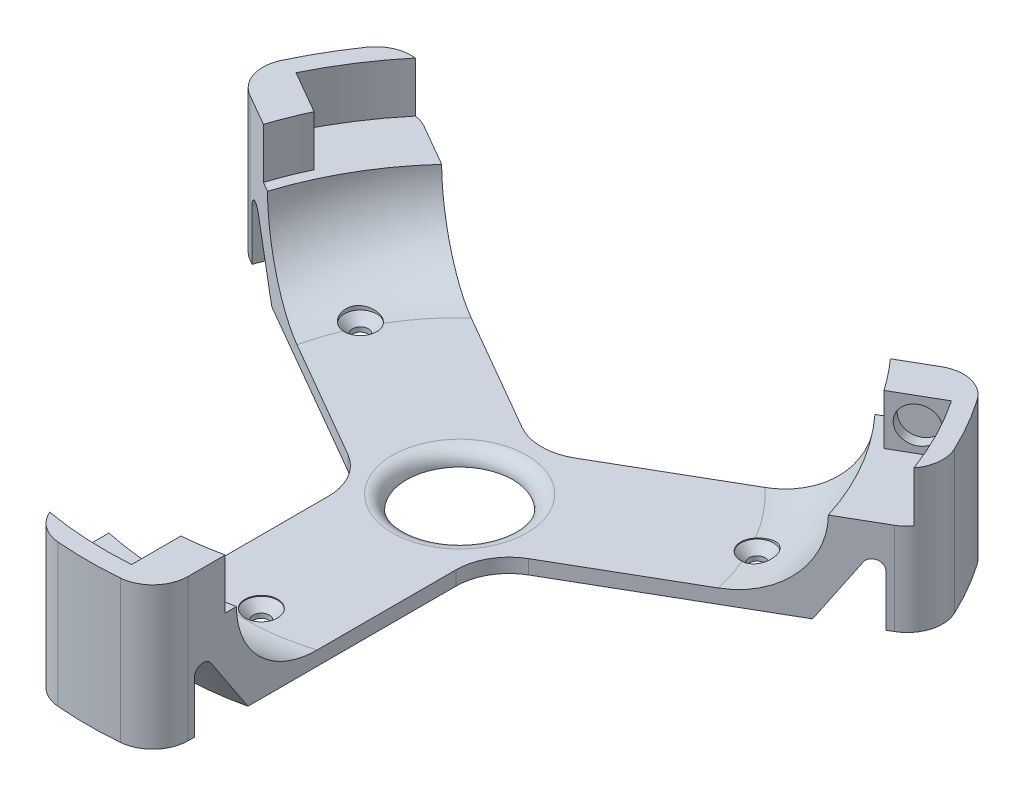
SolidWorks part; units mm, degrees
ref_plane "Front Plane" through (0, 0, 0) normal (0, 0, 1) x (1, 0, 0)
ref_plane "Top Plane" through (0, 0, 0) normal (0, 1, 0) x (1, 0, 0)
ref_plane "Right Plane" through (0, 0, 0) normal (1, 0, 0) x (0, 0, -1)
sketch "Sketch1" plane through (0, 0, 0) normal (0, 1, 0) x (1, 0, 0)
  line L0 (-56, 0) -> (-56, 28)
  line L1 (-28, 0) -> (-28, 28)
  line L3 (-28, 0) -> (-28, 28)
  line L4 (28, 0) -> (28, 28)
  line L5 (28, 0) -> (28, 28)
  line L7 (56, 0) -> (56, 28)
  line L8 (0, 0) -> (0, 28)
  line L9 (56, 0) -> (56, 28)
  line L10 (-56, 28) -> (-56, 56)
  line L11 (-56, 56) -> (-28, 56)
  line L12 (-28, 28) -> (-28, 56)
  line L13 (-28, 28) -> (-28, 56)
  line L15 (0, 56) -> (28, 56)
  line L16 (28, 28) -> (28, 56)
  line L17 (28, 28) -> (28, 56)
  line L18 (28, 56) -> (56, 56)
  line L19 (56, 28) -> (56, 56)
  line L20 (-28, 56) -> (0, 56)
  line L21 (56, 28) -> (56, 56)
  line L23 (0, 28) -> (0, 56)
  line L24 (-56, -28) -> (-56, 0)
  line L25 (-28, -28) -> (-28, 0)
  line L27 (-28, -28) -> (-28, 0)
  line L28 (28, -28) -> (28, 0)
  line L29 (28, -28) -> (28, 0)
  line L31 (56, -28) -> (56, 0)
  line L32 (0, -28) -> (0, 0)
  line L33 (56, -28) -> (56, 0)
  line L34 (-56, 0) -> (-56, 28)
  line L35 (-56, 28) -> (-28, 28)
  line L36 (-28, 0) -> (-28, 28)
  line L37 (-28, 0) -> (-28, 28)
  line L38 (0, 0) -> (0, 28)
  line L39 (0, 28) -> (28, 28)
  line L40 (28, 0) -> (28, 28)
  line L41 (28, 0) -> (28, 28)
  line L42 (28, 28) -> (56, 28)
  line L43 (56, 0) -> (56, 28)
  line L44 (-28, 28) -> (0, 28)
  line L45 (56, 0) -> (56, 28)
  line L46 (0, 0) -> (0, 28)
  line L47 (0, 0) -> (0, 28)
  line L48 (28, -56) -> (56, -56)
  line L49 (0, -56) -> (28, -56)
  line L51 (0, -28) -> (28, -28)
  line L52 (28, -56) -> (28, -28)
  line L53 (28, -56) -> (28, -28)
  line L54 (-28, -56) -> (0, -56)
  line L55 (56, -56) -> (56, -28)
  line L56 (-56, -56) -> (-28, -56)
  line L57 (56, -56) -> (56, -28)
  line L58 (-56, -56) -> (-56, -28)
  line L59 (-56, -28) -> (-28, -28)
  line L60 (28, -28) -> (56, -28)
  line L61 (0, -28) -> (28, -28)
  line L62 (0, -28) -> (0, 0)
  line L63 (0, 0) -> (28, 0)
  line L64 (28, -28) -> (28, 0)
  line L65 (28, -28) -> (28, 0)
  line L66 (28, 0) -> (56, 0)
  line L67 (56, -28) -> (56, 0)
  line L68 (-28, -56) -> (-28, -28)
  line L69 (56, -28) -> (56, 0)
  line L70 (-28, -56) -> (-28, -28)
  line L72 (84, 0) -> (84, 28)
  line L81 (0, -56) -> (0, -28)
  line L82 (-28, -28) -> (0, -28)
  line L83 (-56, -28) -> (-28, -28)
  line L84 (-56, -28) -> (-56, 0)
  line L85 (-56, 0) -> (-28, 0)
  line L86 (-28, -28) -> (-28, 0)
  line L87 (-28, -28) -> (-28, 0)
  line L88 (-28, 0) -> (0, 0)
  line L89 (0, -28) -> (0, 0)
  line L90 (0, -28) -> (0, 0)
  line L92 (0, -56) -> (0, -28)
  line L93 (0, -28) -> (0, 0)
  line L94 (0, 0) -> (0, 28)
  line L95 (0, 28) -> (0, 56)
  dimension "D3" = 3
  dimension "D4" = 2
  dimension "D5" = 3
  dimension "D6" = 2
sketch "Sketch2" plane through (0, 0, 0) normal (0, 1, 0) x (1, 0, 0)
  circle A0 centre (0, 0) radius 83
  circle A1 centre (0, 0) radius 105
  dimension "D1" = 166
  dimension "D2" = 22
extrude "Boss-Extrude1" add sketch "Sketch2" along normal blind 22
sketch "Sketch4" plane through (0, 0, 0) normal (0, 0, 1) x (1, 0, 0)
  line L2 (105, 22) -> (-105, 22) construction
  line L3 (-105, 0) -> (105, 0) construction
  line L4 (83, 22) -> (83, 0)
  line L5 (83, 0) -> (61, 0)
  ellipse E0 centre (61, 22) end of major axis (61, 44) minor radius 22 (61, 0) -> (83, 22) ccw
  dimension "D1" = 22
revolve "Revolve5" add sketch "Sketch4" angle 360 about axis through (0, 22, 0) along (0, -1, 0)
sketch "Sketch5" plane through (0, 0, 0) normal (0, -1, 0) x (1, 0, 0)
  circle A0 centre (0, 0) radius 105
  circle A1 centre (0, 0) radius 105 construction
extrude "Boss-Extrude2" add sketch "Sketch5" along normal blind 4
sketch "Sketch6" plane through (0, -4, 0) normal (0, -1, 0) x (1, 0, 0)
  line L0 (18, 10.3923) -> (18, 58.2838)
  line L1 (18, 58.2838) -> (18, 148.9161)
  line L2 (-18, 10.3923) -> (-18, 58.2838)
  line L3 (0, -20.7846) -> (41.4752, -44.7304)
  line L4 (18, 10.3923) -> (59.4752, -13.5534)
  line L5 (59.4752, -13.5534) -> (137.9651, -58.8696)
  line L6 (0, -20.7846) -> (-41.4752, -44.7304)
  line L7 (-18, 10.3923) -> (-59.4752, -13.5534)
  line L8 (41.4752, -44.7304) -> (119.9651, -90.0465)
  line L9 (-59.4752, -13.5534) -> (-137.9651, -58.8696)
  line L10 (-41.4752, -44.7304) -> (-119.9651, -90.0465)
  line L11 (-18, 58.2838) -> (-18, 148.9161)
  arc A0 (137.9651, -58.8696) -> (18, 148.9161) centre (0, 0) ccw
  arc A1 (-119.9651, -90.0465) -> (119.9651, -90.0465) centre (0, 0) ccw
  arc A2 (-18, 148.9161) -> (-137.9651, -58.8696) centre (0, 0) ccw
  dimension "D1" = 3
extrude "Cut-Extrude1" cut sketch "Sketch6" against normal through all
sketch "Sketch9" plane through (0, 0, 0) normal (0, 1, 0) x (1, 0, 0)
  circle A0 centre (0, -56) radius 4.6
  circle A1 centre (-56, 28) radius 4.6
  circle A2 centre (56, 28) radius 4.6
  dimension "D1" = 9.2
  dimension "D2" = 9.2
  dimension "D3" = 9.2
extrude "Cut-Extrude2" cut sketch "Sketch9" along normal blind 20 and the other way blind 0.25
sketch "Sketch15" plane through (0, 0, 0) normal (0, 1, 0) x (1, 0, 0)
  circle A0 centre (0, 0) radius 15
  dimension "D1" = 30
extrude "Cut-Extrude5" cut sketch "Sketch15" against normal blind 12
fillet "Fillet1" radius 15 3 edges at (0, -2, -20.7846) (-18, -2, 10.3923) (18, -2, 10.3923)
fillet "Fillet2" radius 10 6 edges at (-80.5866, 9, -67.3113) (-98.5866, 9, -36.1344) (18, 9, 103.4456) (-18, 9, 103.4456) (98.5866, 9, -36.1344) (80.5866, 9, -67.3113)
fillet "Fillet4" radius 4 1 edges at (0, 0, 15)
hole_wizard "CSK for M4 Flat Head Machine Screw3" positions "3DSketch3" profile "Sketch14" countersink size "M4" standard "ANSI Metric" end condition through all
sketch3d "3DSketch3"
  line L0 (0, -0.25, 56) -> (0, 0, 56) construction
  line L1 (-56, -0.25, -28) -> (-56, 0, -28) construction
  line L2 (56, -0.25, -28) -> (56, 0, -28) construction
  point P0 (0, -0.25, 56)
  point P4 (-56, -0.25, -28)
  point P8 (56, -0.25, -28)
sketch "Sketch14" plane through (0, -0.25, 56) normal (1, 0, 0) x (0, 0, 1)
  line L0 (0, 0) -> (0, 3.75)
  line L1 (0, 3.75) -> (2.25, 3.75)
  line L2 (2.25, 3.75) -> (2.25, 2.45)
  line L3 (2.25, 2.45) -> (4.7, 0)
  line L5 (4.7, 0) -> (0, 0)
  line L6 (-2.25, 2.45) -> (-4.7, 0) construction
  line L11 (0, -6.35) -> (0, 107.95) construction
  dimension "Thru Hole Dia." = 4.5
  dimension "Thru Hole Depth" = 3.75
  dimension "Near C'Sink Dia." = 9.4
  dimension "Near C'Sink Angle" = 90
sketch "Sketch16" plane through (0, 22, 0) normal (0, 1, 0) x (1, 0, 0)
  line L0 (0, 0) -> (-90.9327, 52.5) construction
  line L1 (-89.934, 43.725) -> (-77.8608, 36.7546)
  line L4 (-61.1694, 56.1008) -> (-72.9802, 62.9197)
  line L5 (-90.9802, 31.7428) -> (-79.1694, 24.9239)
  line L7 (-90.9802, 31.7428) -> (-81.9171, 26.5103)
  arc A0 (-86.1886, 59.971) -> (-95.0307, 44.656) centre (0, 0) ccw construction
  arc A1 (-77.8608, 36.7546) -> (-81.9171, 26.5103) centre (0, 0) ccw
  arc A2 (-76.6906, 64.176) -> (-89.934, 43.725) centre (0, 0) ccw
  arc A3 (-61.1694, 56.1008) -> (-79.1694, 24.9239) centre (0, 0) ccw construction
  arc A8 (-72.9802, 62.9197) -> (-86.1886, 59.971) centre (-77.9802, 54.2595) ccw
  arc A9 (-86.1886, 59.971) -> (-95.0307, 44.656) centre (0, 0) ccw
  arc A10 (-95.0307, 44.656) -> (-90.9802, 31.7428) centre (-85.9802, 40.4031) ccw
  arc A11 (-61.1694, 56.1008) -> (-79.1694, 24.9239) centre (0, 0) ccw
  arc A12 (-76.6906, 64.176) -> (-86.1886, 59.971) centre (-77.9802, 54.2595) ccw
  arc A13 (-86.1886, 59.971) -> (-95.0307, 44.656) centre (0, 0) ccw
  arc A14 (-95.0307, 44.656) -> (-90.9802, 31.7428) centre (-85.9802, 40.4031) ccw
  dimension "D1" = 17
  dimension "D5" = 3.1
  dimension "D3" = 7.1
  dimension "D4" = 0
extrude "Boss-Extrude4" add sketch "Sketch16" along normal blind 14.2
sketch "Sketch18" plane through (-3.55, 0, 6.1488) normal (0.5, 0, -0.866) x (-0.866, 0, -0.5)
  line L0 (85.8068, 36.2) -> (85.8068, 22) construction
  line L1 (85.8068, 22) -> (99.7476, 22) construction
  circle A0 centre (92.8068, 29) radius 5.1
  dimension "D1" = 7
  dimension "D2" = 7
  dimension "D3" = 10.2
extrude "Cut-Extrude6" cut sketch "Sketch18" against normal blind 3.1
pattern_circular "CirPattern1" count 3 over 360 about axis through (0, 22, 0) along (0, -1, 0) of "Boss-Extrude4", "Cut-Extrude6"
ref_plane "Plane1" through (0, 0, 0) normal (-1, 0, 0) x (0, 0, 1)
sketch "Sketch19" plane through (0, 0, 0) normal (-1, 0, 0) x (0, 0, 1)
  line L0 (94.6626, -4) -> (79.8263, -4)
  line L1 (94.6626, -4) -> (19.0526, -4) construction
  line L2 (79.8263, -4) -> (94.6626, 18.9399)
  line L3 (94.6626, 36.2) -> (94.6626, -4) construction
  line L4 (94.6626, 18.9399) -> (94.6626, -4)
revolve "Cut-Revolve1" cut sketch "Sketch19" angle 360 about axis through (0, 22, 0) along (0, -1, 0)
fillet "Fillet5" radius 2.5 3 edges at (-81.9802, 18.9399, -47.3313) (81.9802, 18.9399, -47.3313) (0, 18.9399, 94.6626)
